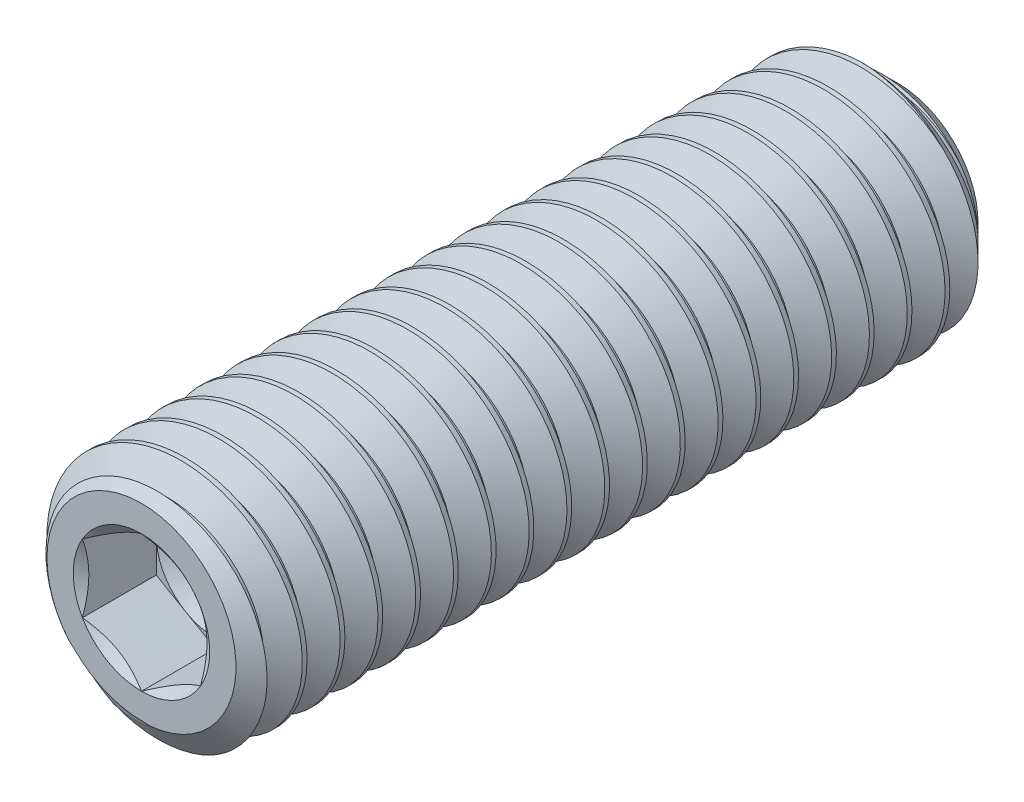
SolidWorks part; units mm, degrees
ref_plane "Front" through (0, 0, 0) normal (0, 0, 1) x (1, 0, 0)
ref_plane "Top" through (0, 0, 0) normal (0, 1, 0) x (1, 0, 0)
ref_plane "Right" through (0, 0, 0) normal (1, 0, 0) x (0, 0, -1)
sketch "Body Sketch" plane through (0, 0, 0) normal (1, 0, 0) x (0, 0, -1)
  line L0 (-8, 0) -> (-8, 2)
  line L1 (-8, 2) -> (-7.6499, 2.5)
  line L2 (-7.6499, 2.5) -> (7.2, 2.5)
  line L3 (7.2, 2.5) -> (8, 1.7)
  line L4 (-0.2249, 2.5) -> (-0.2249, -2.5) construction
  line L5 (8, 0) -> (-8, 0)
  line L6 (-8, 2) -> (-8, -2) construction
  line L7 (8, 0) -> (8, 1.7)
  point P11 (-0.2249, 0)
  dimension "Length" = 16
  dimension "Top Chamfer" = 35
  dimension "D6" = 45
  dimension "Diameter" = 5
  dimension "D1" = 4
  dimension "Tip Chamfer" = 0.8
revolve "Body Revolve" add sketch "Body Sketch" angle 360 about L5
ref_plane "Bottom of Tip Plane" through (0, 0, -8) normal (0, 0, 1) x (1, 0, 0)
sketch "Spiral Sketch" plane through (0, 0, -8) normal (0, 0, 1) x (1, 0, 0)
  circle A0 centre (0, 0) radius 2.5 construction
  circle A1 centre (0, 0) radius 2.5
curve "Helix/Spiral" pitch 0.8 height 16.8 radius 2.5 centre (0, 0, -8) axis (0, 0, 1) start towards (0, 1, 0) parameters "Thread Pitch"=0.8
sketch "Cut Sweep Sketch" plane through (0, 0, 0) normal (1, 0, 0) x (0, 0, -1)
  line L0 (8, 2.5) -> (8.7, 2.5)
  line L1 (8.7, 2.5) -> (8.4, 1.9804)
  line L2 (8.4, 1.9804) -> (8.3, 1.9804)
  line L3 (8.3, 1.9804) -> (8, 2.5)
  line L4 (8.15, 2.2402) -> (8.55, 2.2402) construction
  line L6 (-7.6499, 2.5) -> (7.2, 2.5) construction
  dimension "D1" = 0.1
  dimension "D3" = 60
  dimension "D2" = 0.4
sweep "Cut Sweep" cut profiles "Cut Sweep Sketch" path "Helix/Spiral" align with end faces yes
sketch "Hex Sketch" plane through (0, 0, 8) normal (0, 0, 1) x (1, 0, 0)
  line L1 (0, 1.4434) -> (-1.25, 0.7217)
  line L2 (-1.25, 0.7217) -> (-1.25, -0.7217)
  line L3 (-1.25, -0.7217) -> (0, -1.4434)
  line L4 (0, -1.4434) -> (1.25, -0.7217)
  line L5 (1.25, -0.7217) -> (1.25, 0.7217)
  line L6 (1.25, 0.7217) -> (0, 1.4434)
  circle A0 centre (0, 0) radius 1.25 construction
  dimension "Hex" = 2.5
extrude "Hex Extrude" cut sketch "Hex Sketch" against normal blind 1.5625
sketch "Hex Entry Sketch" plane through (0, 0, 8) normal (0, 0, 1) x (1, 0, 0)
  circle A0 centre (0, 0) radius 1.4434
extrude "Hex Entry Extrude" cut sketch "Hex Entry Sketch" against normal through all draft 55
sketch "Hex Bottom Sketch" plane through (0, 0, 6.4375) normal (0, 0, 1) x (1, 0, 0)
  circle A0 centre (0, 0) radius 1.25 construction
  circle A1 centre (0, 0) radius 1.25
extrude "Hex Bottom Extrude" cut sketch "Hex Bottom Sketch" against normal through all draft 60
equation "\"D1@Cut Sweep Sketch\" = \"Thread Pitch@Helix/Spiral\" * .125"
equation "\"D2@Cut Sweep Sketch\" = \"Thread Pitch@Helix/Spiral\" * .5"
equation "\"D3@Helix/Spiral\" = \"Length@Body Sketch\" + \"Thread Pitch@Helix/Spiral\""
equation "\"hex Depth@Hex Extrude\" = \"Hex@Hex Sketch\" * .625"
equation "\"D1@Body Sketch\" = \"Diameter@Body Sketch\" * .8"
equation "\"Diameter\"= 5mm"
equation "\"Thread Pitch\"= 0.8mm"
equation "\"Hex Size\"= 2.5mm"
equation "\"Diameter@Body Sketch\"=\"Diameter\""
equation "\"Thread Pitch@Helix/Spiral\"=\"Thread Pitch\""
equation "\"Hex@Hex Sketch\"=\"Hex Size\""
equation "\"Tip Chamfer@Body Sketch\"=\"Thread Pitch@Helix/Spiral\""
